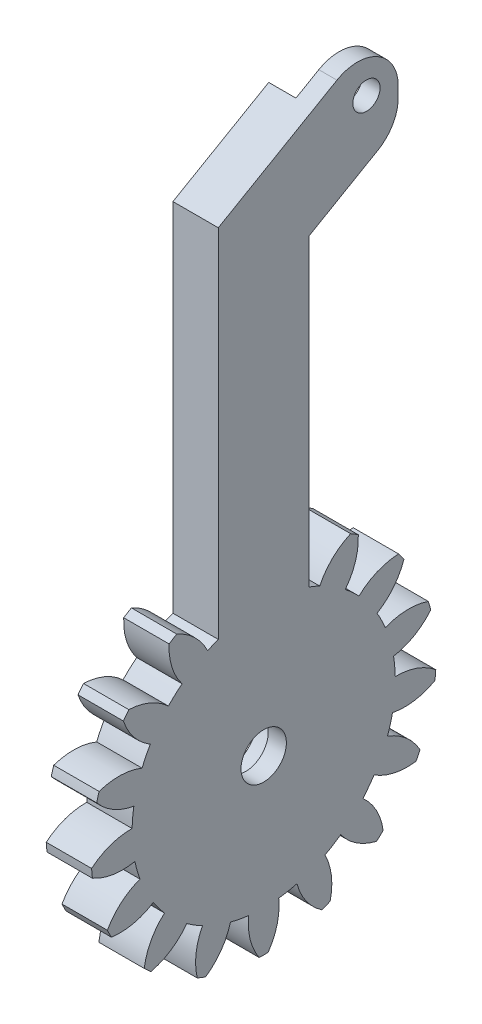
SolidWorks part; units mm, degrees
ref_plane "Plane1" through (0, 0, 0) normal (0, 0, 1) x (1, 0, 0)
ref_plane "Plane2" through (0, 0, 0) normal (0, 1, 0) x (1, 0, 0)
ref_plane "Plane3" through (0, 0, 0) normal (1, 0, 0) x (0, 0, -1)
sketch "HoldingSke" plane through (0, 0, 0) normal (0, 1, 0) x (1, 0, 0)
  line L0 (0, 0) -> (0.4782, -0.1462)
  line L1 (-15, 0) -> (100, 0) construction
  line L2 (0, 0) -> (-2.1039, 2.3779)
  line L3 (0, 0) -> (-11.863, 4.5341)
  line L4 (0, 0) -> (8.2586, 2.5249)
  line L5 (0, 0) -> (-46.8476, -17.4728)
  line L6 (0, 0) -> (-8.2896, -5.593)
  line L7 (-2.1039, 2.3779) -> (8.659, 51.2077)
  line L8 (-76.2, 54.61) -> (-75.3, 54.61)
  line L9 (-71.009, 38.7566) -> (-53.1078, 45.2721)
  line L10 (-76.2, 71.12) -> (104.1128, 71.12)
  line L11 (0, 0) -> (-10, 0)
  line L12 (-76.2, 101.6) -> (-76.133, 101.6)
  line L13 (24.9733, 27.94) -> (52.9518, 28.4284)
  line L14 (24.9733, 27.94) -> (24.9743, 27.94)
  line L15 (24.9733, 27.94) -> (100.4006, 29.5858)
  line L16 (-63.627, -2) -> (-12.827, -2)
  circle A0 centre (0, 0) radius 2.5
  circle A1 centre (0, 0) radius 14.499
  circle A2 centre (0, 0) radius 37.5
  circle A3 centre (0, 0) radius 2.5
  dimension "Num_teeth" = 17
  dimension "Pitch_radius" = 180.3128
  dimension "Width" = 10
  dimension "Thickness" = 10
sketch "BasProSke" plane through (0, 0, 0) normal (0, 1, 0) x (1, 0, 0)
  line L0 (-10, 0) -> (60, 0) construction
  line L1 (0, 0) -> (0, 19)
  line L2 (0, 0) -> (10, 0)
  line L3 (10, 0) -> (10, 19)
  line L4 (10, 19) -> (0, 19)
  dimension "Thickness" = 10
  dimension "Diameter" = 38
revolve "Base-Revolve" add sketch "BasProSke" angle 360 about L0
sketch "TooCutSke" plane through (0, 0, 0) normal (1, 0, 0) x (0, 0, -1)
  line L1 (0, 0) -> (0, 107) construction
  line L2 (0, 0) -> (-1.6857, 16.9162) construction
  line L3 (0, 0) -> (-6.2247, 33.2991) construction
  line L4 (-1.6857, 16.9162) -> (-3.1123, 16.6495) construction
  arc A0 (1.0204, 14.4631) -> (-1.0204, 14.4631) centre (0, 0) ccw
  arc A1 (3.0261, 18.7832) -> (-3.0261, 18.7832) centre (0, 0) ccw
  circle A2 centre (0, 0) radius 17 construction
  circle A3 centre (0, 0) radius 15.9748 construction
  arc A4 (-1.0204, 14.4631) -> (-3.0261, 18.7832) centre (-7.8003, 13.9409) ccw
  arc A5 (3.0261, 18.7832) -> (1.0204, 14.4631) centre (7.8003, 13.9409) ccw
extrude "ToothCut" cut sketch "TooCutSke" along normal through all
fillet "Breaks" [suppressed] radius 0.04 tangent propagation no
fillet "RootFillets" [suppressed] radius 0.501
pattern_circular "TeethCuts" count 17 every 21.176 about axis through (-10, 0, 0) along (1, 0, 0) of "ToothCut", "RootFillets", "Breaks"
sketch "HubNeaOneSke" plane through (0, 0, 0) normal (-1, 0, 0) x (0, 0, 1)
  circle A0 centre (0, 0) radius 14.499
  dimension "Diameter" = 28.998
extrude "HubNearOne" [suppressed] add sketch "HubNeaOneSke" along normal blind 40.0019
sketch "HubNeaBotSke" plane through (0, 0, 0) normal (-1, 0, 0) x (0, 0, 1)
  circle A0 centre (0, 0) radius 14.499
  dimension "Diameter" = 28.998
extrude "HubNearBoth" [suppressed] add sketch "HubNeaBotSke" along normal blind 20.0009
ref_plane "FarPln" through (10, 0, 0) normal (1, 0, 0) x (0, 0, -1)
sketch "HubFarSke" plane through (10, 0, 0) normal (1, 0, 0) x (0, 0, -1)
  circle A0 centre (0, 0) radius 14.499
  dimension "Diameter" = 28.998
extrude "HubFar" [suppressed] add sketch "HubFarSke" along normal blind 20.0009
sketch "BorSke" plane through (0, 0, 0) normal (1, 0, 0) x (0, 0, -1)
  circle A0 centre (0, 0) radius 2.5
  dimension "Diameter" = 5
extrude "Bore" cut sketch "BorSke" along normal mid plane 100.0038
sketch "KeySke" plane through (0, 0, 0) normal (1, 0, 0) x (0, 0, -1)
  line L0 (-1, 0) -> (-1, 3.4)
  line L1 (-1, 3.4) -> (1, 3.4)
  line L2 (1, 3.4) -> (1, 0)
  line L3 (0, 0) -> (0, 34) construction
  line L4 (-1, 0) -> (1, 0)
  dimension "Width" = 2
extrude "Keyway" [suppressed] cut sketch "KeySke" along normal mid plane 100.0038
pattern_circular "Keyway2" [suppressed] count 2 every 90 about axis through (-10, 0, 0) along (1, 0, 0)
sketch "Sketch1" plane through (0, 0, 0) normal (0, 0, 1) x (1, 0, 0)
  line L1 (-5, 20) -> (5, 20)
  line L2 (-5, 20) -> (-5, -20)
  line L3 (-5, -20) -> (5, -20)
  line L4 (5, 20) -> (5, -20)
  line L5 (-5, 20) -> (5, -20) construction
  line L6 (-5, -20) -> (5, 20) construction
  point P0 (0, 0)
  dimension "D1" = 10
  dimension "D2" = 40
extrude "Cut-Extrude1" cut sketch "Sketch1" against normal blind 20 and the other way blind 20
sketch "Sketch2" plane through (5, 0, 0) normal (-1, 0, 0) x (0, 0, 1)
  line L0 (0, 0) -> (0, -21.0725) construction
  line L1 (-3.961, -0.5571) -> (-2, -14.5)
  line L2 (4, 0) -> (2, -14.5)
  circle A0 centre (0, 0) radius 4
  circle A1 centre (0, -14.5) radius 2
  dimension "D1" = 8
  dimension "D2" = 4
  dimension "D3" = 14.5
sketch "Sketch4" plane through (10, 0, 0) normal (1, 0, 0) x (0, 0, -1)
  line L0 (0, 0) -> (0, 50) construction
  line L1 (0, 50) -> (17.3205, 60) construction
  line L2 (5, 0) -> (5, 47.1132)
  line L3 (5, 47.1132) -> (14.8205, 52.7831)
  line L4 (-5, 0) -> (-5, 52.8868)
  line L5 (-5, 52.8868) -> (14.8205, 64.3301)
  line L6 (14.8205, 64.3301) -> (14.8205, 52.7831)
  line L7 (-5, 0) -> (-2.5, 0)
  line L8 (5, 47.1132) -> (19.8205, 55.6699) construction
  line L9 (2.5, 0) -> (5, 0)
  circle A0 centre (0, 0) radius 2.5 construction
  arc A1 (2.5, 0) -> (-2.5, 0) centre (0, 0) ccw
  dimension "D1" = 120
  dimension "D2" = 50
  dimension "D3" = 20
  dimension "D4" = 5
  dimension "D5" = 5
extrude "Boss-Extrude1" add sketch "Sketch4" against normal blind 5
sketch "Sketch5" plane through (5, 0, 0) normal (-1, 0, 0) x (0, 0, 1)
  circle A0 centre (0, 0) radius 2.5 construction
  circle A1 centre (0, 0) radius 2.5
  circle A2 centre (0, 0) radius 4.75
  dimension "D1" = 9.5
extrude "Cut-Extrude2" cut sketch "Sketch5" against normal blind 3
sketch "Sketch6" plane through (5, 0, 0) normal (-1, 0, 0) x (0, 0, 1)
  line L1 (-14.8205, 52.7831) -> (-14.8205, 64.3301) construction
  circle A0 centre (-11.3205, 57.3301) radius 1.5
  dimension "D1" = 3
  dimension "D2" = 7
  dimension "D3" = 3.5
extrude "Cut-Extrude3" cut sketch "Sketch6" against normal through all
sketch "Sketch7" plane through (5, 0, 0) normal (-1, 0, 0) x (0, 0, 1)
  line L0 (-11.3205, 57.3301) -> (-18.8552, 61.6803) construction
  line L1 (-14.8205, 64.3301) -> (5, 52.8868) construction
  line L2 (-8.3205, 62.5263) -> (-15.8552, 66.8765)
  line L3 (-14.3205, 52.134) -> (-21.8552, 56.4842)
  line L4 (-21.8552, 56.4842) -> (-15.8552, 66.8765)
  circle A0 centre (-11.3205, 57.3301) radius 6
  dimension "D1" = 12
  dimension "D2" = 6
  dimension "D3" = 6
extrude "Cut-Extrude4" cut sketch "Sketch7" against normal blind 3 contours A0 L0 L4 L3 | A0 | L0 A0 L2 L4 region at (5, 57.5087, -18.7016) region at (5, 63.6331, -15.1657) region at (5, 62.9618, -12.8295)
fillet "Fillet1" radius 4.5 2 edges at (9, 52.7831, -14.8205) (9, 64.3301, -14.8205)
fillet "Fillet2" radius 4.5 1 edges at (6.5, 51.4493, -12.5102)
equation "' \"Module@HoldingSke\" = 6.35"
equation "' \"Num_teeth@HoldingSke\" = 12"
equation "' \"Ap@HoldingSke\" =  20"
equation "' \"Ap@HoldingSke\" = 20"
equation "'\"Width@HoldingSke\" = 0.2.5 * 25.4"
equation "' \"Hub_dia@HoldingSke\"= 1 * 25.4"
equation "' \"Hub_dia@HoldingSke\" = 1 * 25.4"
equation "' \"Overall_len@HoldingSke\" = 1.0 * 25.4"
equation "' \"Bore@HoldingSke\" = 0.75 * 25.4"
equation "' \"T_dim@HoldingSke\" = 0.1 * 25.4"
equation "' \"Width@KeySke\" = 0.25 * 25.4"
equation "' \"Show_teeth@HoldingSke\" = 13"
equation "' \"Backlash@HoldingSke\" = 0.009 * 25.4"
equation "' \"Addendum_fac@HoldingSke\" = 1.0"
equation "' \"Dedendum_fac@HoldingSke\" = 1.25"
equation "' \"Dedendum_add@HoldingSke\" = 0.00005 * 25.4"
equation "' \"Clearance_fac@HoldingSke\" = 0.25"
equation "\"Pitch@HoldingSke\" = 1 / \"Module@HoldingSke\""
equation "\"Overcut_dia@TooCutSke\" = (\"Num_teeth@HoldingSke\" + 2 * \"Addendum_fac@HoldingSke\") / \"Pitch@HoldingSke\" + 0.002 * 25.4"
equation "\"Pitch_dia@TooCutSke\" = \"Num_teeth@HoldingSke\" / \"Pitch@HoldingSke\""
equation "\"Base_dia@TooCutSke\" = \"Num_teeth@HoldingSke\" / \"Pitch@HoldingSke\" * cos((\"Ap@HoldingSke\"  * 3.14159265 / 180))"
equation "\"Root_dia@TooCutSke\" = (\"Num_teeth@HoldingSke\" + 2) / \"Pitch@HoldingSke\" - 2 * (\"Addendum_fac@HoldingSke\" + \"Dedendum_fac@HoldingSke\") / \"Pitch@HoldingSke\" - \"Dedendum_add@HoldingSke\" * 2"
equation "\"Half_ang@TooCutSke\" = 180 / \"Num_teeth@HoldingSke\""
equation "\"Half_CT@TooCutSke\" = \"Num_teeth@HoldingSke\" / \"Pitch@HoldingSke\" * sin((3.14159265 / 2 / \"Num_teeth@HoldingSke\")) / 2 - 7 * \"Backlash@HoldingSke\" / 4"
equation "\"Flank_rad@TooCutSke\" = \"Num_teeth@HoldingSke\" / \"Pitch@HoldingSke\" / 5"
equation "\"Radius@RootFillets\" = \"Clearance_fac@HoldingSke\" / \"Pitch@HoldingSke\" + \"Dedendum_add@HoldingSke\""
equation "\"Break_rad@Breaks\" = 0.02 / \"Pitch@HoldingSke\""
equation "\"Thickness@HoldingSke\" = \"Width@HoldingSke\""
equation "\"OAL@HoldingSke\" = \"Thickness@HoldingSke\""
equation "\"MHD@HoldingSke\" = (\"Num_teeth@HoldingSke\" + 2) / \"Pitch@HoldingSke\" - 2 * (\"Addendum_fac@HoldingSke\" + \"Dedendum_fac@HoldingSke\")  / \"Pitch@HoldingSke\" - \"Dedendum_add@HoldingSke\" * 2"
equation "\"MBD@HoldingSke\" = (\"Num_teeth@HoldingSke\" + 2) / \"Pitch@HoldingSke\" - 2 * (\"Addendum_fac@HoldingSke\" + \"Dedendum_fac@HoldingSke\")  / \"Pitch@HoldingSke\" - \"Dedendum_add@HoldingSke\" * 2 - 0.002 * 25.4"
equation "\"MHD@HoldingSke\" = ((sgn( \"MHD@HoldingSke\" - \"Hub_dia@HoldingSke\" )-1)*( \"MHD@HoldingSke\" - \"Hub_dia@HoldingSke\" ))/-2+ \"Hub_dia@HoldingSke\""
equation "\"MBD@HoldingSke\" = ((sgn( \"MBD@HoldingSke\" - \"Bore@HoldingSke\" )-1)*( \"MBD@HoldingSke\" - \"Bore@HoldingSke\" ))/-2+ \"Bore@HoldingSke\""
equation "\"OAL@HoldingSke\" = ((sgn( \"OAL@HoldingSke\" - \"Overall_len@HoldingSke\" )+1)*( \"OAL@HoldingSke\" - \"Overall_len@HoldingSke\" ))/2 + \"Overall_len@HoldingSke\" + 0.000002 * 25.4"
equation "\"Num_teeth@TeethCuts\" = int( \"Show_teeth@HoldingSke\" ) + 1"
equation "\"Num_teeth@TeethCuts\" = ((sgn( \"Num_teeth@TeethCuts\" - \"Num_teeth@HoldingSke\" )-1)*( \"Num_teeth@TeethCuts\" - \"Num_teeth@HoldingSke\" ))/-2+ \"Num_teeth@HoldingSke\""
equation "\"Num_teeth@TeethCuts\" = ((sgn( \"Num_teeth@TeethCuts\" - 2.0)+1)*( \"Num_teeth@TeethCuts\" - 2.0))/2 +2.0"
equation "\"Angle@TeethCuts\" = 360.0 / \"Num_teeth@HoldingSke\""
equation "\"Diameter@BasProSke\" = (\"Num_teeth@HoldingSke\" + 2 * \"Addendum_fac@HoldingSke\") / \"Pitch@HoldingSke\""
equation "\"Thickness@BasProSke\"  = \"Thickness@HoldingSke\""
equation "' \"Fillet_rad@BasProSke\" =  \"Thickness@HoldingSke\" * 0.05"
equation "' \"Fillet_rad@BasProSke\" = \"Thickness@HoldingSke\" * 0.05"
equation "\"MHD@HoldingSke\" = ((sgn( \"MHD@HoldingSke\" - \"Root_dia@TooCutSke\" )-1)*( \"MHD@HoldingSke\" - \"Root_dia@TooCutSke\" ))/-2+ \"Root_dia@TooCutSke\""
equation "\"Diameter@HubNeaOneSke\" = \"MHD@HoldingSke\""
equation "\"Length@HubNearOne\" = \"OAL@HoldingSke\" - \"Thickness@BasProSke\""
equation "\"Diameter@HubNeaBotSke\" = \"MHD@HoldingSke\""
equation "\"Length@HubNearBoth\" = ( \"OAL@HoldingSke\" - \"Thickness@BasProSke\" ) / 2.0"
equation "\"Thickness@FarPln\" = \"Thickness@BasProSke\""
equation "\"Diameter@HubFarSke\" = \"MHD@HoldingSke\""
equation "\"Length@HubFar\" = ( \"OAL@HoldingSke\" - \"Thickness@BasProSke\" ) / 2.0"
equation "\"Diameter@BorSke\" = \"MBD@HoldingSke\""
equation "\"D1@Bore\" = \"OAL@HoldingSke\" * 2.0"
equation "\"D1@Keyway\" = \"OAL@HoldingSke\" * 2.0"
equation "\"Offset@KeySke\" = \"T_dim@HoldingSke\" + \"MBD@HoldingSke\" / 2.0"
